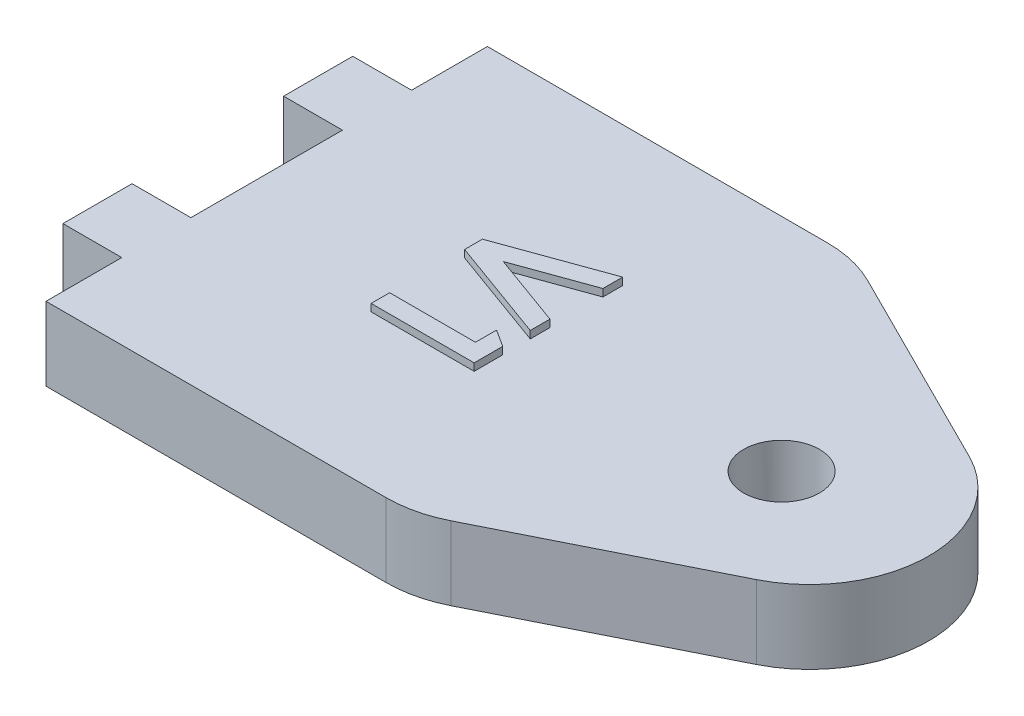
SolidWorks part; units mm, degrees
ref_plane "Front Plane" through (0, 0, 0) normal (0, 0, 1) x (1, 0, 0)
ref_plane "Top Plane" through (0, 0, 0) normal (0, 1, 0) x (1, 0, 0)
ref_plane "Right Plane" through (0, 0, 0) normal (1, 0, 0) x (0, 0, -1)
sketch "Sketch1" plane through (0, 0, 0) normal (0, 1, 0) x (1, 0, 0)
  line L0 (0, 0) -> (0, 10)
  line L13 (0, 10) -> (-8, 10)
  line L14 (-8, 10) -> (-8, 20)
  line L16 (-8, 20) -> (0, 20)
  line L17 (0, 20) -> (0, 40)
  line L18 (0, 40) -> (-8, 40)
  line L19 (-8, 40) -> (-8, 50)
  line L20 (-8, 50) -> (0, 50)
  line L21 (0, 50) -> (0, 60)
  line L22 (0, 60) -> (50, 60)
  line L23 (50, 60) -> (90, 40)
  line L24 (90, 40) -> (90, 20)
  line L25 (90, 20) -> (50, 0)
  line L26 (50, 0) -> (0, 0)
  dimension "D1" = 10
  dimension "D2" = 10
  dimension "D3" = 20
  dimension "D4" = 10
  dimension "D5" = 10
  dimension "D6" = 8
  dimension "D7" = 8
  dimension "D8" = 50
  dimension "D9" = 40
  dimension "D10" = 50
  dimension "D11" = 20
  dimension "D12" = 20
extrude "Boss-Extrude2" add sketch "Sketch1" along normal blind 10
sketch "Sketch5" plane through (0, 10, 0) normal (0, 1, 0) x (1, 0, 0)
  line L0 (90, 40) -> (50, 60) construction
  line L1 (50, 0) -> (90, 20) construction
  line L2 (90, 20) -> (90, 40) construction
  line L3 (81.0557, 44.4721) -> (90, 40)
  line L4 (90, 40) -> (90, 20)
  line L5 (90, 20) -> (81.0557, 15.5279)
  arc A0 (81.0557, 44.4721) -> (81.0557, 15.5279) centre (73.8197, 30) cw
  line M2 (50, 0) -> (90, 20)
  line M3 (90, 20) -> (90, 40)
  line M4 (90, 40) -> (50, 60)
extrude "Cut-Extrude2" cut sketch "Sketch5" against normal blind 10 contours A0 L4 M4 | A0 M3 M2 region at (88.1125, 10, -21.1665) region at (88.1125, 10, -38.8335)
fillet "Fillet3" radius 16 2 edges at (50, 5, -60) (50, 5, 0)
sketch "Sketch6" plane through (0, 10, 0) normal (0, 1, 0) x (1, 0, 0)
  line L0 (23.3477, 50.0906) -> (23.3477, 8.6725) construction
  arc A0 (81.0557, 15.5279) -> (81.0557, 44.4721) centre (73.8197, 30) ccw construction
  circle A1 centre (70, 30) radius 5.15
  text T0 "<b>V1</b>" font "Century Gothic" height 14
  point P5 (90, 30)
  dimension "D5" = 10.3
  dimension "D1" = 20
sketch "Sketch8" plane through (0, 10, 0) normal (0, 1, 0) x (1, 0, 0)
  line L0 (-8, 50) -> (-8, 40) construction
  line L1 (0, 50) -> (-8, 50)
  line L2 (0, 50) -> (0, 49.7)
  line L3 (0, 49.7) -> (-8, 49.7)
  line L4 (-8, 50) -> (-8, 49.7)
  line L6 (0, 40) -> (-8, 40)
  line L7 (0, 40) -> (0, 40.3)
  line L8 (0, 40.3) -> (-8, 40.3)
  line L9 (-8, 40) -> (-8, 40.3)
  line L11 (-8, 20) -> (-8, 19.7)
  line L12 (0, 19.7) -> (-8, 19.7)
  line L13 (0, 20) -> (0, 19.7)
  line L14 (0, 20) -> (-8, 20)
  line L15 (-8, 10) -> (-8, 10.3)
  line L16 (0, 10.3) -> (-8, 10.3)
  line L17 (0, 10) -> (0, 10.3)
  line L18 (0, 10) -> (-8, 10)
  dimension "D1" = 0.3
  dimension "D2" = 0.3
extrude "Cut-Extrude5" cut sketch "Sketch8" against normal blind 10
extrude "Boss-Extrude3" add sketch "Sketch6" along normal blind 1
sketch "Sketch9" plane through (0, 11, 0) normal (0, 1, 0) x (1, 0, 0)
  circle A0 centre (70, 30) radius 5.15
extrude "Cut-Extrude7" cut sketch "Sketch9" against normal through all both and the other way through all
